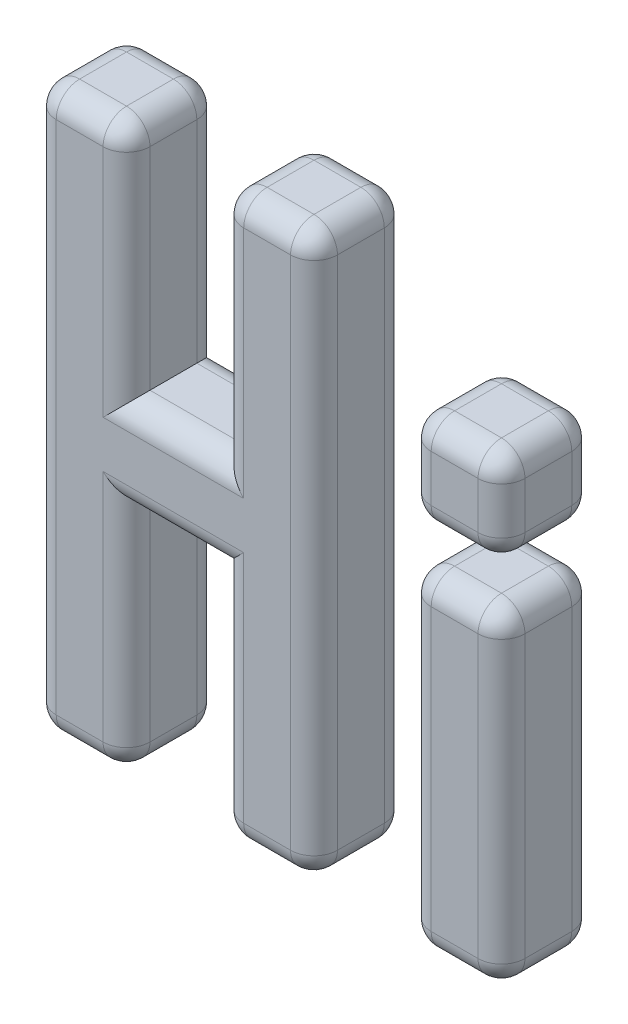
SolidWorks part; units mm, degrees
ref_plane "Front Plane" through (0, 0, 0) normal (0, 0, 1) x (1, 0, 0)
ref_plane "Top Plane" through (0, 0, 0) normal (0, 1, 0) x (1, 0, 0)
ref_plane "Right Plane" through (0, 0, 0) normal (1, 0, 0) x (0, 0, -1)
sketch "Sketch1" plane through (0, 0, 0) normal (0, 0, 1) x (1, 0, 0)
  line L0 (-86.338, 15.2817) -> (-86.338, -9.7183)
  line L1 (-96.338, 50.2817) -> (-66.338, 50.2817)
  line L2 (-96.338, 50.2817) -> (-96.338, -9.7183)
  line L3 (-96.338, -9.7183) -> (-66.338, -9.7183)
  line L4 (-66.338, 50.2817) -> (-66.338, -9.7183)
  line L9 (-96.338, 50.2817) -> (-86.338, 50.2817)
  line L10 (-96.338, 50.2817) -> (-96.338, -9.7183)
  line L11 (-96.338, -9.7183) -> (-86.338, -9.7183)
  line L12 (-86.338, 50.2817) -> (-86.338, 25.2817)
  line L13 (-66.338, 50.2817) -> (-76.338, 50.2817)
  line L14 (-66.338, 50.2817) -> (-66.338, -9.7183)
  line L15 (-66.338, -9.7183) -> (-76.338, -9.7183)
  line L16 (-76.338, 50.2817) -> (-76.338, 25.2817)
  line L17 (-86.338, 25.2817) -> (-76.338, 25.2817)
  line L18 (-96.338, 25.2817) -> (-96.338, 15.2817)
  line L19 (-86.338, 15.2817) -> (-76.338, 15.2817)
  line L20 (-66.338, 25.2817) -> (-66.338, 15.2817)
  line L21 (-56.338, 25.2817) -> (-46.338, 25.2817)
  line L22 (-56.338, 25.2817) -> (-56.338, -9.7183)
  line L23 (-56.338, -9.7183) -> (-46.338, -9.7183)
  line L24 (-46.338, 25.2817) -> (-46.338, -9.7183)
  line L25 (-56.338, 39.6338) -> (-46.338, 39.6338)
  line L26 (-56.338, 39.6338) -> (-56.338, 29.6338)
  line L27 (-56.338, 29.6338) -> (-46.338, 29.6338)
  line L28 (-46.338, 39.6338) -> (-46.338, 29.6338)
  line L29 (-76.338, 15.2817) -> (-76.338, -9.7183)
  dimension "D1" = 30
  dimension "D2" = 60
  dimension "D3" = 10
  dimension "D4" = 10
  dimension "D5" = 25
  dimension "D6" = 25
  dimension "D7" = 10
  dimension "D8" = 10
  dimension "D9" = 35
  dimension "D10" = 10
  dimension "D11" = 10
extrude "Boss-Extrude1" add sketch "Sketch1" along normal blind 10 contours L19 L29 L3 L4 L14 L1 L16 L17 L12 L2 L10 L0 | L28 L25 L26 L27 | L24 L21 L22 L23 region at (-81.338, 20.2817, 0) region at (-51.338, 7.7817, 0) region at (-51.338, 34.6338, 0)
fillet "Fillet2" radius 2.5 1 edges at (-96.338, 50.2817, 5)
fillet "Fillet3" radius 2.5 1 edges at (-86.338, 50.2817, 5)
fillet "Fillet4" radius 2.5 1 edges at (-66.338, 50.2817, 5)
fillet "Fillet5" radius 2.5 1 edges at (-76.338, 50.2817, 5)
fillet "Fillet6" radius 2.5 1 edges at (-96.338, -9.7183, 5)
fillet "Fillet7" radius 2.5 1 edges at (-86.338, -9.7183, 5)
fillet "Fillet8" radius 2.5 1 edges at (-46.338, -9.7183, 5)
fillet "Fillet9" radius 2.5 1 edges at (-66.338, -9.7183, 5)
fillet "Fillet10" radius 2.5 1 edges at (-76.338, -9.7183, 5)
fillet "Fillet11" radius 2.5 1 edges at (-56.338, -9.7183, 5)
fillet "Fillet12" radius 2.5 1 edges at (-46.338, 25.2817, 5)
fillet "Fillet13" radius 2.5 1 edges at (-46.338, 29.6338, 5)
fillet "Fillet14" radius 2.5 3 edges at (-56.338, 29.6338, 5) (-56.338, 39.6338, 5) (-46.338, 39.6338, 5)
fillet "Fillet15" radius 2.5 1 edges at (-56.338, 25.2817, 5)
fillet "Fillet16" radius 2.5 9 edges at (-86.338, 36.5317, 10) (-87.0703, 49.5495, 10) (-91.338, 50.2817, 10) (-95.6058, 49.5495, 10) (-86.338, 4.0317, 10) (-87.0703, -8.9861, 10) (-91.338, -9.7183, 10) (-95.6058, -8.9861, 10) (-96.338, 20.2817, 10)
fillet "Fillet17" radius 2.5 9 edges at (-76.338, 36.5317, 10) (-75.6058, 49.5495, 10) (-71.338, 50.2817, 10) (-67.0703, 49.5495, 10) (-76.338, 4.0317, 10) (-75.6058, -8.9861, 10) (-71.338, -9.7183, 10) (-67.0703, -8.9861, 10) (-66.338, 20.2817, 10)
fillet "Fillet18" radius 2.5 8 edges at (-47.0703, 24.5495, 10) (-51.338, 25.2817, 10) (-55.6058, 24.5495, 10) (-55.6058, -8.9861, 10) (-51.338, -9.7183, 10) (-47.0703, -8.9861, 10) (-56.338, 7.7817, 10) (-46.338, 7.7817, 10)
fillet "Fillet19" radius 2.5 8 edges at (-55.6058, 38.9016, 10) (-56.338, 34.6338, 10) (-55.6058, 30.366, 10) (-47.0703, 30.366, 10) (-46.338, 34.6338, 10) (-47.0703, 38.9016, 10) (-51.338, 29.6338, 10) (-51.338, 39.6338, 10)
fillet "Fillet20" radius 2.5 8 edges at (-47.0703, 38.9016, 0) (-55.6058, 38.9016, 0) (-56.338, 34.6338, 0) (-55.6058, 30.366, 0) (-51.338, 29.6338, 0) (-47.0703, 30.366, 0) (-51.338, 39.6338, 0) (-46.338, 34.6338, 0)
fillet "Fillet21" radius 2.5 8 edges at (-47.0703, 24.5495, 0) (-51.338, 25.2817, 0) (-55.6058, 24.5495, 0) (-55.6058, -8.9861, 0) (-51.338, -9.7183, 0) (-47.0703, -8.9861, 0) (-56.338, 7.7817, 0) (-46.338, 7.7817, 0)
fillet "Fillet22" radius 2.5 17 edges at (-86.338, 36.5317, 0) (-87.0703, 49.5495, 0) (-91.338, 50.2817, 0) (-95.6058, 49.5495, 0) (-86.338, 4.0317, 0) (-87.0703, -8.9861, 0) (-91.338, -9.7183, 0) (-95.6058, -8.9861, 0) (-76.338, 36.5317, 0) (-75.6058, 49.5495, 0) (-67.0703, 49.5495, 0) (-76.338, 4.0317, 0) (-75.6058, -8.9861, 0) (-71.338, -9.7183, 0) (-67.0703, -8.9861, 0) (-96.338, 20.2817, 0) (-66.338, 20.2817, 0)
fillet "Fillet23" radius 2.5 2 edges at (-81.338, 15.2817, 0) (-81.338, 25.2817, 0)
fillet "Fillet24" radius 2.5 2 edges at (-81.338, 15.2817, 10) (-81.338, 25.2817, 10)
